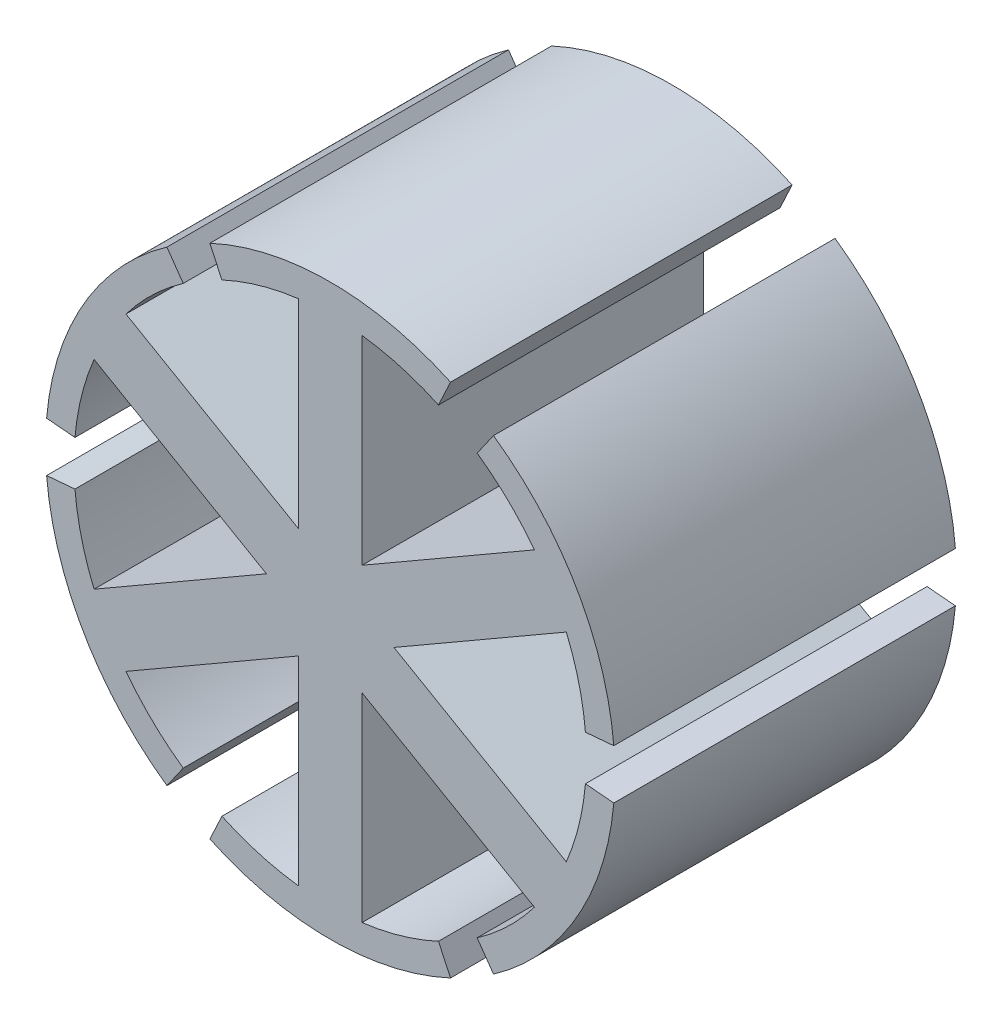
SolidWorks part; units mm, degrees
ref_plane "Front" through (0, 0, 0) normal (0, 0, 1) x (1, 0, 0)
ref_plane "Top" through (0, 0, 0) normal (0, 1, 0) x (1, 0, 0)
ref_plane "Right" through (0, 0, 0) normal (1, 0, 0) x (0, 0, -1)
sketch "Sketch1" plane through (0, 0, 0) normal (0, 0, 1) x (1, 0, 0)
  line L0 (0, 0) -> (25, 0) construction
  line L1 (0, 0) -> (12.5, 21.6506) construction
  line L2 (0, 0) -> (-12.5, 21.6506) construction
  line L3 (0, 0) -> (-25, 0) construction
  line L5 (0, 0) -> (-12.5, -21.6506) construction
  line L6 (0, 0) -> (12.5, -21.6506) construction
  line L7 (0, 0) -> (21.6506, 12.5) construction
  line L8 (5.6, 0) -> (20.7341, 8.7377) construction
  line L9 (2.8, 4.8497) -> (17.9341, 13.5874) construction
  line L10 (0, 0) -> (14.3394, 20.4788) construction
  line L14 (0, 0) -> (24.9049, 2.1789) construction
  line L16 (0, 0) -> (10.5655, 22.6577) construction
  line L17 (0, 0) -> (24.9049, -2.1789) construction
  circle A4 centre (0, 0) radius 25 construction
  circle A5 centre (0, 0) radius 22.5 construction
  circle A6 centre (0, 0) radius 5.6 construction
  circle A7 centre (0, 0) radius 4.6 construction
  dimension "D1" = 11.2
  dimension "D2" = 9.2
  dimension "D3" = 50
  dimension "D4" = 45
sketch "Sketch2" plane through (0, 0, 0) normal (0, 0, 1) x (1, 0, 0)
  line L0 (2.8, 4.8497) -> (17.9341, 13.5874)
  line L1 (5.6, 0) -> (20.7341, 8.7377)
  line L2 (0, 0) -> (14.3394, 20.4788) construction
  line L3 (0, 0) -> (24.9049, 2.1789) construction
  line L4 (22.4144, 1.961) -> (24.9049, 2.1789)
  line L5 (12.9055, 18.4309) -> (14.3394, 20.4788)
  line L6 (5.6, 0) -> (20.7341, -8.7377)
  line L7 (22.4144, -1.961) -> (24.9049, -2.1789)
  line L8 (12.9055, -18.4309) -> (14.3394, -20.4788)
  line L9 (2.8, -4.8497) -> (17.9341, -13.5874)
  line L10 (2.8, -4.8497) -> (2.8, -22.3251)
  line L11 (9.5089, -20.3919) -> (10.5655, -22.6577)
  line L12 (-9.5089, -20.3919) -> (-10.5655, -22.6577)
  line L13 (-2.8, -4.8497) -> (-2.8, -22.3251)
  line L14 (-2.8, -4.8497) -> (-17.9341, -13.5874)
  line L15 (-12.9055, -18.4309) -> (-14.3394, -20.4788)
  line L16 (-22.4144, -1.961) -> (-24.9049, -2.1789)
  line L17 (-5.6, 0) -> (-20.7341, -8.7377)
  line L18 (-5.6, 0) -> (-20.7341, 8.7377)
  line L19 (-22.4144, 1.961) -> (-24.9049, 2.1789)
  line L20 (-12.9055, 18.4309) -> (-14.3394, 20.4788)
  line L21 (-2.8, 4.8497) -> (-17.9341, 13.5874)
  line L22 (-2.8, 4.8497) -> (-2.8, 22.3251)
  line L23 (-9.5089, 20.3919) -> (-10.5655, 22.6577)
  line L24 (9.5089, 20.3919) -> (10.5655, 22.6577)
  line L25 (2.8, 4.8497) -> (2.8, 22.3251)
  arc A0 (22.4144, -1.961) -> (20.7341, -8.7377) centre (0, 0) cw
  arc A1 (12.9055, 18.4309) -> (17.9341, 13.5874) centre (0, 0) cw
  circle A2 centre (0, 0) radius 22.5 construction
  arc A3 (20.7341, 8.7377) -> (22.4144, 1.961) centre (0, 0) cw
  arc A4 (14.3394, 20.4788) -> (24.9049, 2.1789) centre (0, 0) cw
  arc A5 (24.9049, -2.1789) -> (14.3394, -20.4788) centre (0, 0) cw
  arc A6 (17.9341, -13.5874) -> (12.9055, -18.4309) centre (0, 0) cw
  arc A7 (9.5089, -20.3919) -> (2.8, -22.3251) centre (0, 0) cw
  arc A8 (10.5655, -22.6577) -> (-10.5655, -22.6577) centre (0, 0) cw
  arc A9 (-2.8, -22.3251) -> (-9.5089, -20.3919) centre (0, 0) cw
  arc A10 (-12.9055, -18.4309) -> (-17.9341, -13.5874) centre (0, 0) cw
  arc A11 (-14.3394, -20.4788) -> (-24.9049, -2.1789) centre (0, 0) cw
  arc A12 (-20.7341, -8.7377) -> (-22.4144, -1.961) centre (0, 0) cw
  arc A13 (-22.4144, 1.961) -> (-20.7341, 8.7377) centre (0, 0) cw
  arc A14 (-24.9049, 2.1789) -> (-14.3394, 20.4788) centre (0, 0) cw
  arc A15 (-17.9341, 13.5874) -> (-12.9055, 18.4309) centre (0, 0) cw
  arc A16 (-9.5089, 20.3919) -> (-2.8, 22.3251) centre (0, 0) cw
  arc A17 (-10.5655, 22.6577) -> (10.5655, 22.6577) centre (0, 0) cw
  arc A18 (2.8, 22.3251) -> (9.5089, 20.3919) centre (0, 0) cw
  point P9 (0, 0)
  point P64 (0, 0)
  dimension "D2" = 25
  dimension "D3" = 22.4144
  dimension "D4" = 21.1309
  dimension "D1" = 6
extrude "Boss-Extrude1" add sketch "Sketch2" along normal blind 30
